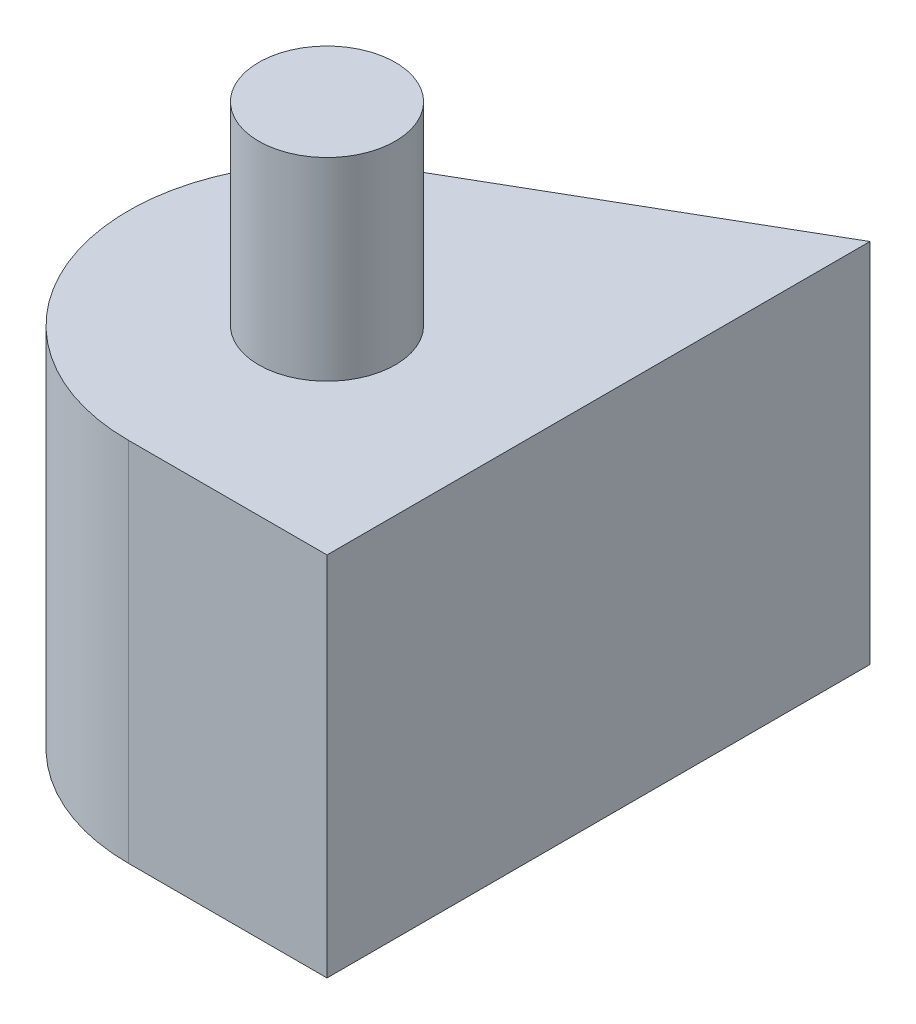
SolidWorks part; units mm, degrees
ref_plane "Plan de face" through (0, 0, 0) normal (0, 0, 1) x (1, 0, 0)
ref_plane "Plan de dessus" through (0, 0, 0) normal (0, 1, 0) x (1, 0, 0)
ref_plane "Plan de droite" through (0, 0, 0) normal (1, 0, 0) x (0, 0, -1)
sketch "Esquisse1" plane through (0, 0, 0) normal (0, 1, 0) x (1, 0, 0)
  line L0 (0, -8) -> (8, -8)
  line L1 (8, -8) -> (8, 13.8564)
  line L2 (8, 13.8564) -> (-4, 6.9282)
  arc A0 (-4, 6.9282) -> (0, -8) centre (0, 0) ccw
  dimension "D2" = 8
  dimension "D1" = 60
  dimension "D3" = 8
extrude "Boss.-Extru.1" add sketch "Esquisse1" along normal blind 14.75
sketch "Esquisse2" plane through (0, 14.75, 0) normal (0, 1, 0) x (1, 0, 0)
  circle A0 centre (0, 0) radius 2.75
  dimension "prong" = 5.5
extrude "Boss.-Extru.6" add sketch "Esquisse2" along normal blind 7.8
extrude "Boss.-Extru.7" add sketch "Esquisse2<4>" against normal blind 17.9
sketch "Esquisse2<4>" plane through (0, 14.75, 0) normal (0, 1, 0) x (1, 0, 0) same geometry as "Esquisse2"
